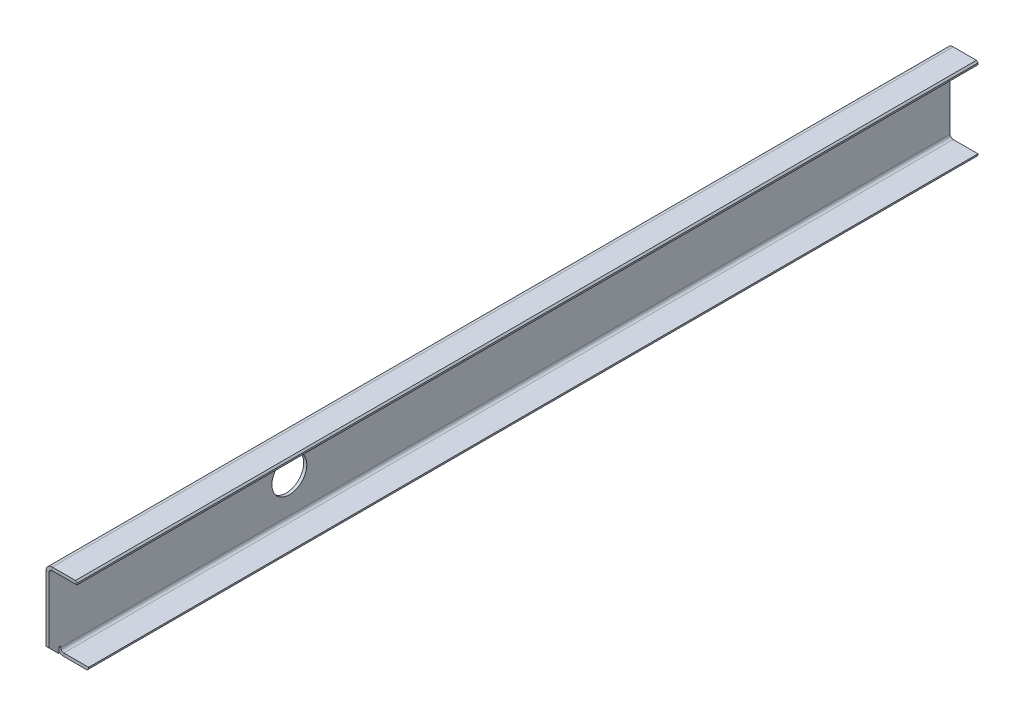
SolidWorks part; units mm, degrees
note: The reader was unsure of these and kept them because the rebuilt part matched: flange length of "边线-法兰1"; thickness of "边线-法兰1".
material "Q460"
ref_plane "前视基准面" through (0, 0, 0) normal (0, 0, 1) x (1, 0, 0)
ref_plane "上视基准面" through (0, 0, 0) normal (0, 1, 0) x (1, 0, 0)
ref_plane "右视基准面" through (0, 0, 0) normal (1, 0, 0) x (0, 0, -1)
sketch "草图1" plane through (0, 0, 0) normal (1, 0, 0) x (0, 0, -1)
  line L0 (0, 0) -> (2325, 0)
  line L1 (2325, 0) -> (2325, -215)
  line L2 (2325, -215) -> (30, -215)
  line L3 (30, -215) -> (0, -185)
  line L4 (0, -185) -> (0, 0)
  dimension "D1" = 215
  dimension "D2" = 30
  dimension "D3" = 30
  dimension "D4" = 2325
base flange "基体-法兰1" sketch "草图1" thickness 8 reverse thickness direction no parameters "D1"=5
edge flange "边线-法兰1" sketch "草图10" flange profiles "草图10", "草图11" flange angle 90 flange length 80 flange position material inside bend radius 8 thickness 8 relief rectangular parameters "D6"=10, "D8"=1
sketch "草图10" plane through (0, 0, 0) normal (0, 1, 0) x (0, 0, 1)
  line L0 (-2325, 0) -> (0, 0) construction
  line L2 (-2325, 0) -> (-2325, 72)
  line L3 (-2325, 72) -> (0, 72)
  line L4 (0, 72) -> (0, 0)
  line L7 (-2325, 0) -> (0, 0)
sketch "草图11" plane through (0, -215, 0) normal (0, -1, 0) x (0, 0, -1)
  line L2 (2325, 0) -> (2325, 72)
  line L3 (2325, 72) -> (30, 72)
  line L4 (30, 72) -> (30, 0)
  line L5 (30, 0) -> (2325, 0) construction
  line L6 (30, 0) -> (2325, 0)
bend "边线折弯1" bend radius 8 bend angle 90 parameters "D5"=1
bend "边线折弯2" bend radius 8 bend angle 90 parameters "D5"=2
chamfer "倒角1" distance 4 angle 45 2 edges at (72, -215, -1177.5) (72, 0, -1162.5)
sketch "草图12" plane through (0, 0, 0) normal (1, 0, 0) x (0, 0, -1)
  line L0 (0, 0) -> (2325, 0) construction
  line L1 (0, -16) -> (0, -185) construction
  circle A0 centre (620, -107.5) radius 45
  dimension "D1" = 90
  dimension "D2" = 107.5
  dimension "D3" = 620
extrude "切除-拉伸1" cut sketch "草图12" against normal through all normal cut yes
sketch "折弯-线1" [suppressed] plane through (0, 0, 0) normal (0, 1, 0) x (1, 0, 0)
sketch "边界框1" [suppressed] plane through (0, 0, 0) normal (0, 1, 0) x (1, 0, 0)
sheet metal parameters "钣金6" thickness 8 parameters "D1"=5
flat pattern "平板型式6" [suppressed]
sketch "折弯-线2" plane through (0, 0, 0) normal (0, 1, 0) x (1, 0, 0)
sketch "边界框2" [suppressed] plane through (0, 0, 0) normal (0, 1, 0) x (1, 0, 0)
sheet metal parameters "钣金7" thickness 8 parameters "D1"=5, "D7"=86
flat pattern "平板型式6" [suppressed]
sketch "折弯-线2" plane through (0, 0, 0) normal (0, 1, 0) x (1, 0, 0)
sketch "边界框2" [suppressed] plane through (0, 0, 0) normal (0, 1, 0) x (1, 0, 0)
bend of the flat pattern "展开-<边线折弯1>1"
bend of the flat pattern "展开-<边线折弯2>1"
sheet metal parameters "钣金10" thickness 8 parameters "D1"=5, "D7"=86
flat pattern "平板型式6" [suppressed]
sketch "折弯-线2" plane through (0, 0, 0) normal (0, 1, 0) x (1, 0, 0)
sketch "边界框2" [suppressed] plane through (0, 0, 0) normal (0, 1, 0) x (1, 0, 0)
bend of the flat pattern "展开-<边线折弯1>1"
bend of the flat pattern "展开-<边线折弯2>1"
